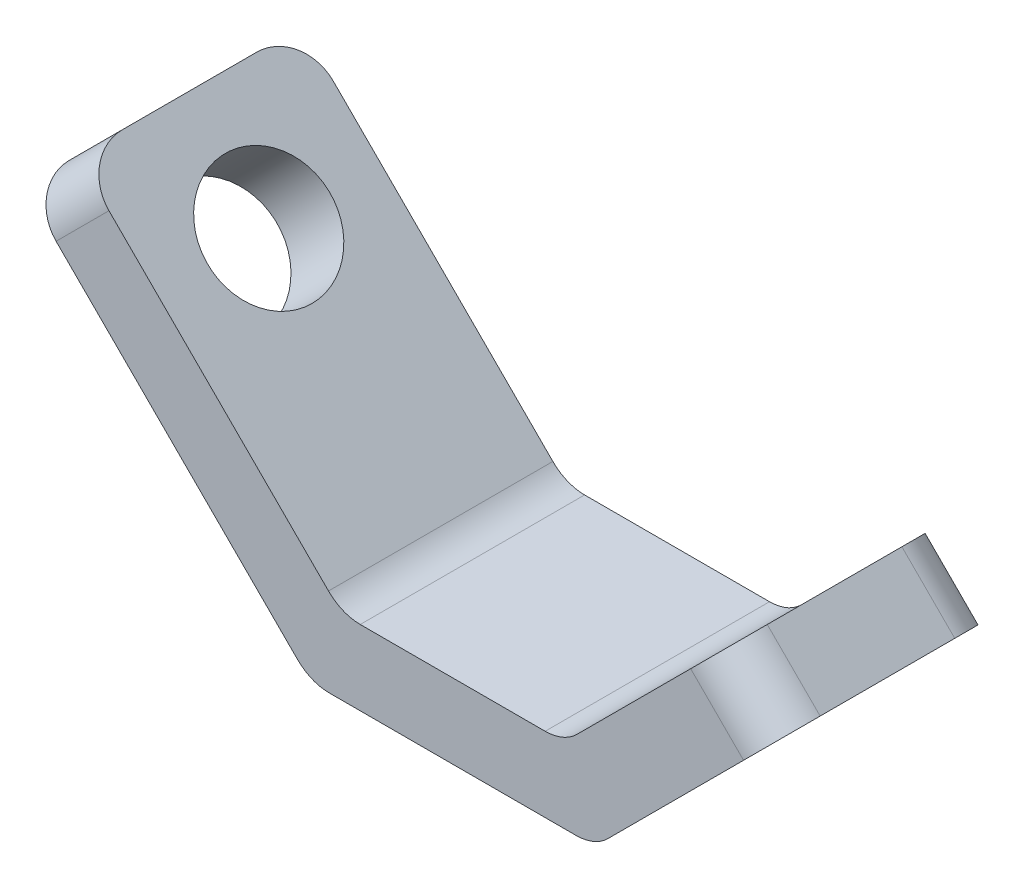
SolidWorks part; units mm, degrees
ref_plane "正面" through (0, 0, 0) normal (0, 0, 1) x (1, 0, 0)
ref_plane "平面" through (0, 0, 0) normal (0, 1, 0) x (1, 0, 0)
ref_plane "右側面" through (0, 0, 0) normal (1, 0, 0) x (0, 0, -1)
sketch "ｽｹｯﾁ1" plane through (0, 0, 0) normal (0, 0, 1) x (1, 0, 0)
  line L0 (0, 0) -> (-19.1421, 19.1421)
  line L1 (-19.1421, 19.1421) -> (-15.6066, 22.6777)
  line L2 (-15.6066, 22.6777) -> (2.0711, 5)
  line L3 (2.0711, 5) -> (16.9203, 5)
  line L4 (16.9203, 5) -> (27.5269, 15.6066)
  line L5 (27.5269, 15.6066) -> (31.0624, 12.0711)
  line L6 (31.0624, 12.0711) -> (18.9914, 0)
  line L7 (18.9914, 0) -> (0, 0)
  point P6 (22.2236, 10.3033)
  dimension "D1" = 135
  dimension "D2" = 135
  dimension "D3" = 5
  dimension "D4" = 5
  dimension "D5" = 5
  dimension "D6" = 25
  dimension "D7" = 15
  dimension "D8" = 18
extrude "ﾎﾞｽ - 押し出し1" add sketch "ｽｹｯﾁ1" along normal mid plane 15
sketch "ｽｹｯﾁ2" plane through (0, 0, 0) normal (-0.7071, -0.7071, 0) x (0, 0, 1)
  line L1 (7.5, 27.0711) -> (-7.5, 27.0711) construction
  circle A0 centre (0, 19.5711) radius 4.1
  dimension "D1" = 8.2
  dimension "D2" = 7.5
extrude "ｶｯﾄ - 押し出し1" cut sketch "ｽｹｯﾁ2" against normal through all both and the other way through all
sketch "ｽｹｯﾁ3" plane through (9.4957, -9.4957, 0) normal (0.7071, -0.7071, 0) x (0, 0, -1)
  line L0 (-7.5, 30.5) -> (-7.5, 15.5) construction
  line L1 (-7.5, 30.5) -> (7.5, 30.5) construction
  circle A0 centre (0, 23) radius 4.1
  point P4 (-7.5, 23)
  point P7 (0, 30.5)
  dimension "D1" = 8.2
extrude "ｶｯﾄ - 押し出し2" cut sketch "ｽｹｯﾁ3" against normal through all both and the other way through all
fillet "ﾌｨﾚｯﾄ1" radius 3 8 edges at (29.2947, 13.8388, -7.5) (29.2947, 13.8388, 7.5) (-17.3744, 20.9099, -7.5) (-17.3744, 20.9099, 7.5) (18.9914, 0, 0) (0, 0, 0) (16.9203, 5, 0) (2.0711, 5, 0)
equation "\"D4@ｽｹｯﾁ1\"=\"D3@ｽｹｯﾁ1\""
equation "\"D5@ｽｹｯﾁ1\"=\"D3@ｽｹｯﾁ1\""
